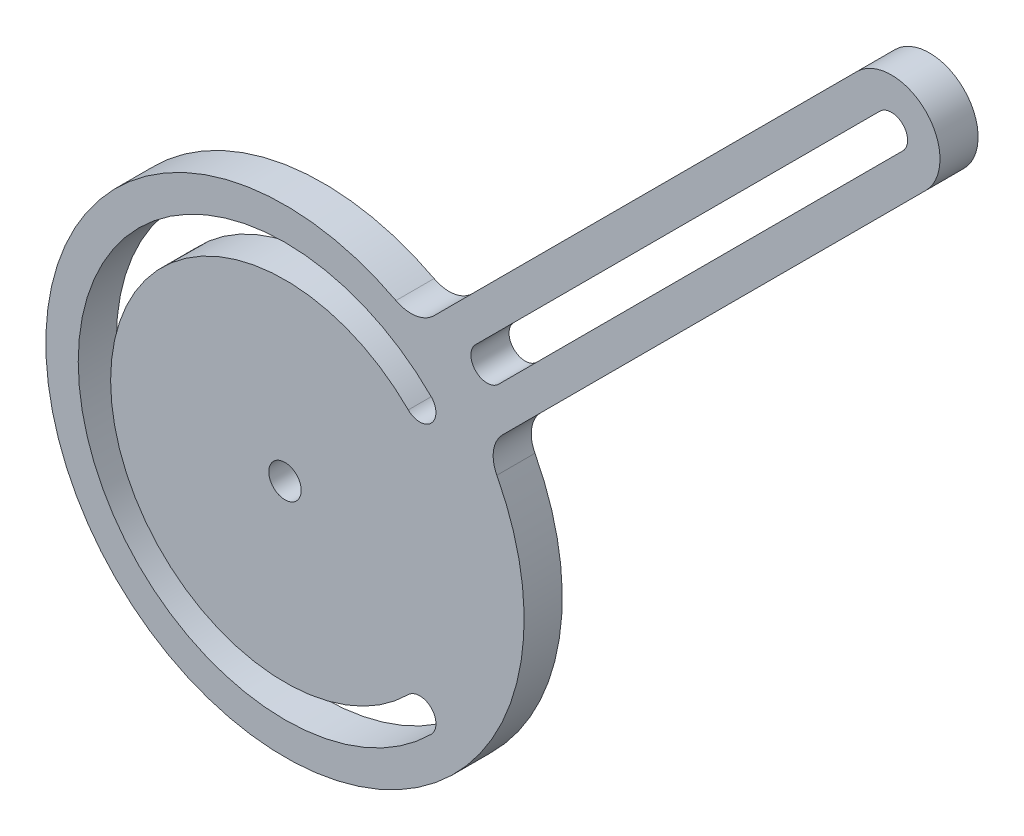
SolidWorks part; units mm, degrees
ref_plane "Front Plane" through (0, 0, 0) normal (0, 0, 1) x (1, 0, 0)
ref_plane "Top Plane" through (0, 0, 0) normal (0, 1, 0) x (1, 0, 0)
ref_plane "Right Plane" through (0, 0, 0) normal (1, 0, 0) x (0, 0, -1)
sketch "Sketch1" plane through (0, 0, 0) normal (0, 0, 1) x (1, 0, 0)
  line L0 (-1000, 0) -> (49000, 0) construction
  line L1 (17.9605, 17.9605) -> (0, 0) construction
  line L2 (17.9605, -17.9605) -> (0, 0) construction
  circle A0 centre (0, 0) radius 2.159
  circle A2 centre (0, 0) radius 31.877
  arc A3 (17.9605, 17.9605) -> (17.9605, -17.9605) centre (0, 0) ccw construction
  arc A4 (19.4872, 19.4872) -> (19.4872, -19.4872) centre (0, 0) ccw
  arc A5 (16.4339, 16.4339) -> (16.4339, -16.4339) centre (0, 0) ccw
  arc A6 (16.4339, 16.4339) -> (19.4872, 19.4872) centre (17.9605, 17.9605) ccw
  arc A7 (19.4872, -19.4872) -> (16.4339, -16.4339) centre (17.9605, -17.9605) ccw
  point P6 (-25.4, 0)
  dimension "D1" = 25.4
  dimension "D2" = 2.159
  dimension "D5" = 4.318
  dimension "D6" = 4.318
  dimension "D3" = 45
  dimension "D4" = 45
extrude "Boss-Extrude1" add sketch "Sketch1" along normal blind 5.08
sketch "Sketch2" plane through (0, 0, 5.08) normal (0, 0, 1) x (1, 0, 0)
  line L0 (0, 0) -> (80.8223, 80.8223) construction
  line L1 (-4.5799, 4.5799) -> (76.2424, 85.4022)
  line L2 (4.5799, -4.5799) -> (85.4022, 76.2424)
  line L3 (-1000, 0) -> (49000, 0) construction
  line L4 (26.9408, 26.9408) -> (80.8223, 80.8223) construction
  line L5 (25.4141, 28.4674) -> (79.2957, 82.3489)
  line L6 (28.4674, 25.4141) -> (82.3489, 79.2957)
  arc A0 (-4.5799, 4.5799) -> (4.5799, -4.5799) centre (0, 0) ccw
  arc A1 (85.4022, 76.2424) -> (76.2424, 85.4022) centre (80.8223, 80.8223) ccw
  arc A3 (25.4141, 28.4674) -> (28.4674, 25.4141) centre (26.9408, 26.9408) ccw
  arc A4 (82.3489, 79.2957) -> (79.2957, 82.3489) centre (80.8223, 80.8223) ccw
  circle A6 centre (0, 0) radius 31.877
  circle A7 centre (0, 0) radius 31.877
  point P3 (40.4112, 40.4112)
  point P9 (34.3515, 34.3515)
  point P13 (26.9408, 26.9408)
  point P16 (53.8815, 53.8815)
  point P21 (0, 0)
  circle M3 centre (0, 0) radius 31.877
  dimension "D3" = 4.318
  dimension "D4" = 2.159
  dimension "D6" = 38.1
  dimension "D1" = 45
  dimension "D2" = 76.2
  dimension "D5" = 0
extrude "Boss-Extrude4" add sketch "Sketch2" against normal blind 5.08 contours L2 A1 L1 A4 L6 A3 L5 M3 region at (47.5644, 55.3281, 5.08)
fillet "Fillet1" radius 4.318 2 edges at (26.6502, 17.4903, 2.54) (17.4903, 26.6502, 2.54)
